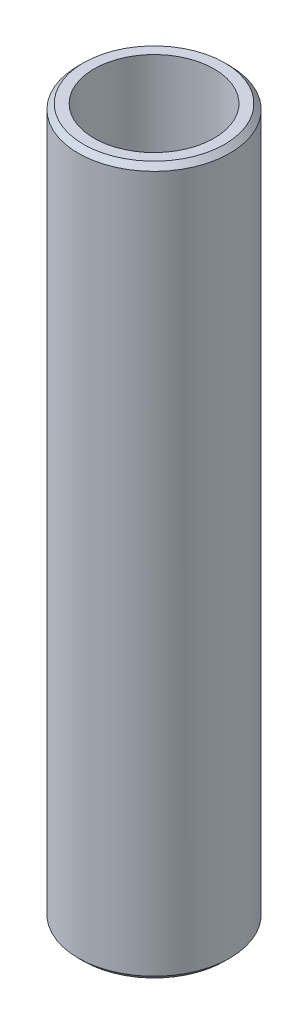
SolidWorks part; units mm, degrees
ref_plane "Front Plane" through (0, 0, 0) normal (0, 0, 1) x (1, 0, 0)
ref_plane "Top Plane" through (0, 0, 0) normal (0, 1, 0) x (1, 0, 0)
ref_plane "Right Plane" through (0, 0, 0) normal (1, 0, 0) x (0, 0, -1)
sketch "Sketch1" plane through (0, 0, 0) normal (0, 1, 0) x (1, 0, 0)
  circle A0 centre (0, 0) radius 52.5
  dimension "SHAFT_OD" = 105
extrude "Boss-Extrude1" add sketch "Sketch1" along normal blind 490.0241
sketch "Sketch2" plane through (0, 0, 0) normal (0, 1, 0) x (1, 0, 0)
  circle A0 centre (0, 0) radius 41.6104
  dimension "BORE_D" = 83.2207
extrude "Cut-Extrude1" cut sketch "Sketch2" along normal through all
chamfer "Chamfer1" distance 3.5799 angle 45 2 edges at (0, 490.0241, 52.5) (0, 0, 52.5)
